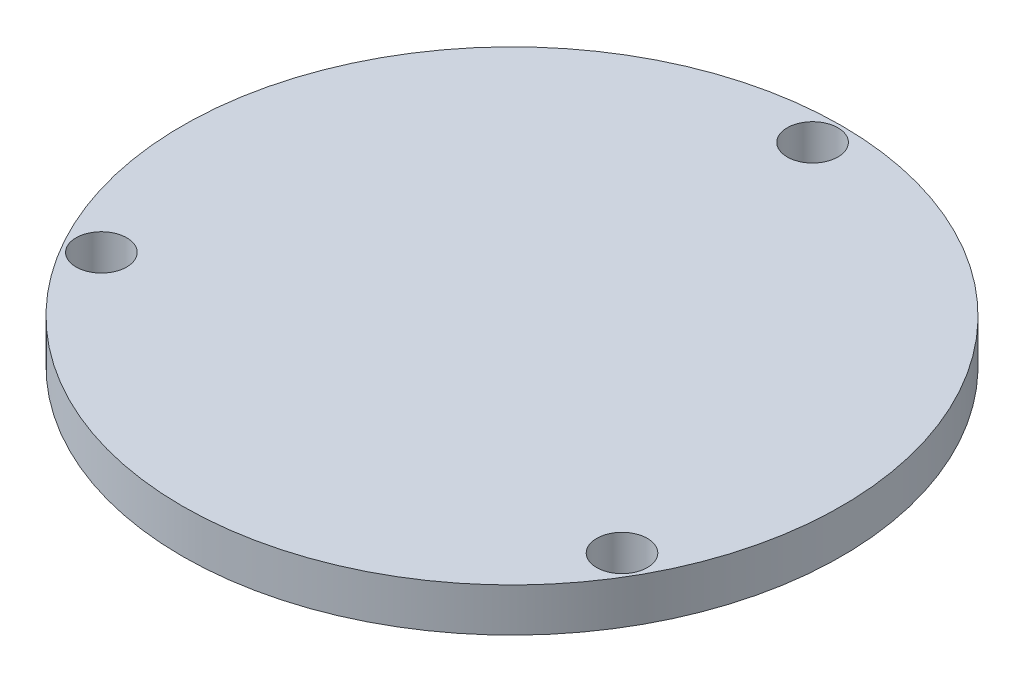
SolidWorks part; units mm, degrees
material "Ceramic Porcelain"
ref_plane "Front Plane" through (0, 0, 0) normal (0, 0, 1) x (1, 0, 0)
ref_plane "Top Plane" through (0, 0, 0) normal (0, 1, 0) x (1, 0, 0)
ref_plane "Right Plane" through (0, 0, 0) normal (1, 0, 0) x (0, 0, -1)
ref_axis "Y Axis" through (0, 0.0762, 0) along (0, -1, 0)
sketch "outter" plane through (0, 0, 0) normal (0, 1, 0) x (1, 0, 0)
  circle A0 centre (0, 0) radius 11.557
  dimension "D1" = 23.114
extrude "Body" add sketch "outter" against normal blind 1.524
sketch "Screw Position" plane through (0, 0, 0) normal (0, 1, 0) x (1, 0, 0)
  point P0 (0, 10.541)
  dimension "D1" = 10.541
hole_wizard "#0 Clearance Hole" positions "Sketch11" profile "Sketch12" hole size "#0" standard "ANSI Inch"
sketch "Sketch11" plane through (0, 0, 0) normal (0, 1, 0) x (-1, 0, 0)
  point P0 (0, -10.541)
sketch "Sketch12" plane through (0, 0, -10.541) normal (1, 0, 0) x (0, 0, 1)
  line L0 (0, 0) -> (0, 2.0582)
  line L1 (0, 2.0582) -> (0.889, 1.524)
  line L2 (0.889, 1.524) -> (0.889, 0)
  line L5 (0.889, 0) -> (0, 0)
  line L10 (0, 2.0582) -> (-0.889, 1.524) construction
  line L11 (0, -6.35) -> (0, 107.95) construction
  dimension "Hole Dia." = 1.778
  dimension "Hole Depth" = 1.524
  dimension "Drill Angle" = 118
pattern_circular "Screw Holes" count 3 over 360 about axis through (0, 0.0762, 0) along (0, -1, 0) of "#0 Clearance Hole"
sketch "IO Positions" plane through (0, 0, 0) normal (0, 1, 0) x (1, 0, 0)
  line L0 (0, 0) -> (-3.4749, 9.5473) construction
  line L1 (0, 0) -> (-5.9719, 8.2196) construction
  point P0 (-3.4749, 9.5473)
  point P5 (-5.9719, 8.2196)
  point P6 (-8.0062, 6.2551)
  point P7 (-9.4202, 3.806)
  point P8 (-10.1043, 1.062)
  point P9 (-10.0056, -1.7643)
  point P13 (10.0056, -1.7643)
  point P14 (10.1043, 1.062)
  point P15 (9.4202, 3.806)
  point P16 (8.0062, 6.2551)
  point P17 (5.9719, 8.2196)
  point P18 (3.4749, 9.5473)
  point P19 (-6.5307, -7.783)
  point P20 (-4.1324, -9.2816)
  point P21 (-1.414, -10.0611)
  point P22 (1.414, -10.0611)
  point P23 (4.1324, -9.2816)
  point P24 (6.5307, -7.783)
  point P25 (0, 0)
  dimension "D3" = 16
  dimension "D2" = 6
  dimension "D4" = 3
equation "\"mount_d\"= 0.91in"
equation "\"dieletric_h\"= 0.06in"
equation "\"D1@outter\" = \"mount_d\""
equation "\"D1@Body\" = \"dieletric_h\""
equation "\"screw_inner_r\"= 0.415in"
equation "\"io_r\"= 0.4in"
equation "\"D1@Screw Position\" = \"screw_inner_r\""
